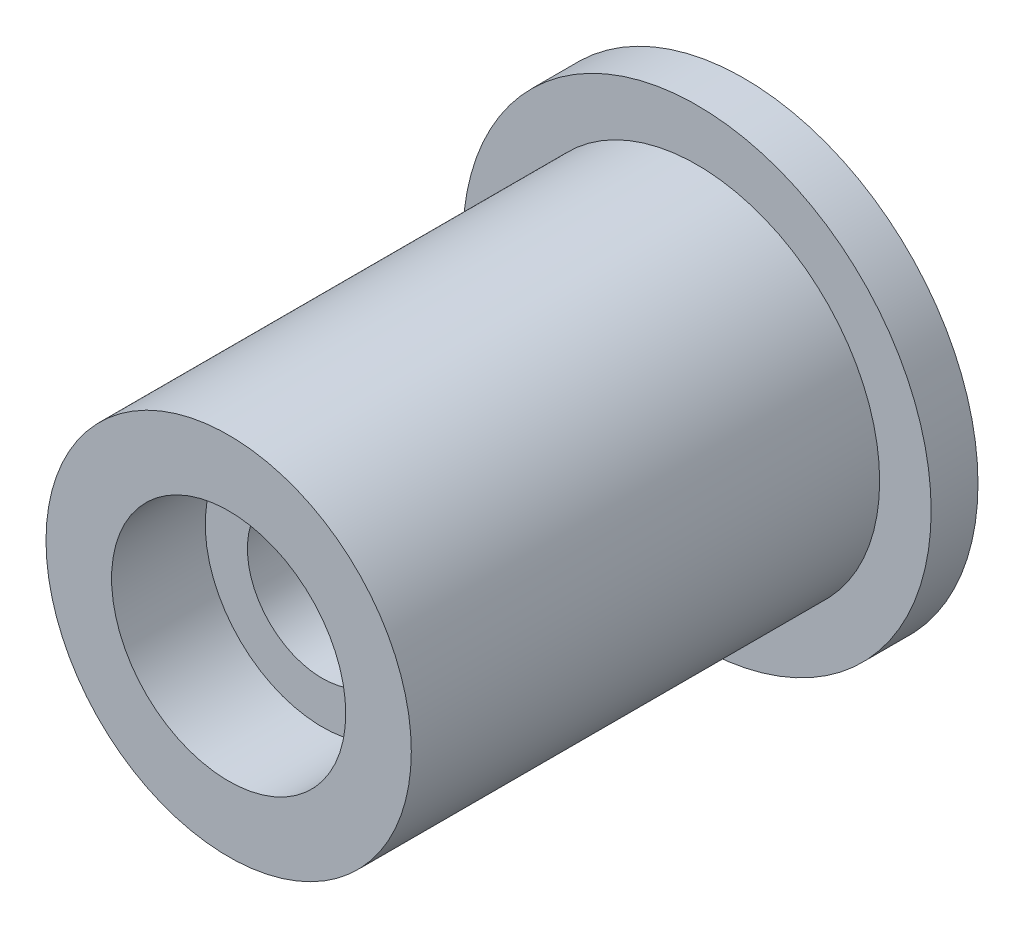
SolidWorks part; units mm, degrees
ref_plane "Front Plane" through (0, 0, 0) normal (0, 0, 1) x (1, 0, 0)
ref_plane "Top Plane" through (0, 0, 0) normal (0, 1, 0) x (1, 0, 0)
ref_plane "Right Plane" through (0, 0, 0) normal (1, 0, 0) x (0, 0, -1)
ref_axis "X" through (-88.99, 0, 0) along (1, 0, 0)
ref_axis "Y" through (0, 55, 0) along (0, -1, 0)
ref_axis "Z" through (0, 0, -88.99) along (0, 0, 1)
sketch "Sketch1" plane through (0, 0, 0) normal (0, 0, 1) x (1, 0, 0)
  circle A0 centre (0, 0) radius 3.9
  circle A1 centre (0, 0) radius 1.6
  circle A2 centre (0, 0) radius 2.5
  circle A3 centre (0, 0) radius 5
  dimension "D1" = 7.8
  dimension "D2" = 3.2
  dimension "D3" = 5
  dimension "D4" = 10
extrude "Boss-Extrude1" add sketch "Sketch1" against normal blind 1 contours A3 | A1
extrude "Boss-Extrude2" add sketch "Sketch1<3>" along normal blind 10 contours A0 A2 region at (-3.7897, 0, 0)
sketch "Sketch1<3>" plane through (0, 0, 0) normal (0, 0, 1) x (1, 0, 0) same geometry as "Sketch1"
extrude "Boss-Extrude3" add sketch "Sketch1<4>" along normal blind 8 contours A2 A1 region at (-2.4293, 0, 0)
sketch "Sketch1<4>" plane through (0, 0, 0) normal (0, 0, 1) x (1, 0, 0) same geometry as "Sketch1"
